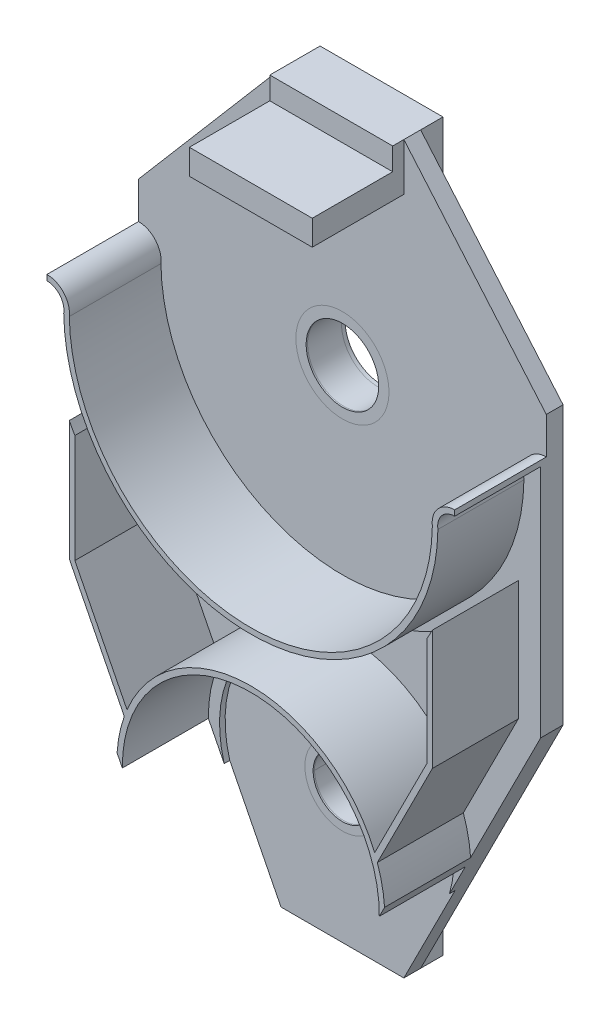
SolidWorks part; units mm, degrees
ref_plane "Piano frontale" through (0, 0, 0) normal (0, 0, 1) x (1, 0, 0)
ref_plane "Piano superiore" through (0, 0, 0) normal (0, 1, 0) x (1, 0, 0)
ref_plane "Piano destro" through (0, 0, 0) normal (1, 0, 0) x (0, 0, -1)
sketch "Piastrone" plane through (0, 0, 0) normal (0, 0, 1) x (1, 0, 0)
  line L0 (-86.2054, 491.905) -> (23.7946, 491.905)
  line L1 (23.7946, 491.905) -> (278.7946, 193.1534)
  line L2 (278.7946, 193.1534) -> (278.7946, -303.2973)
  line L3 (278.7946, -303.2973) -> (23.7946, -808.095)
  line L4 (23.7946, -808.095) -> (-86.2054, -808.095)
  line L5 (-86.2054, 491.905) -> (-86.2054, -808.095) construction
  line L6 (23.7946, -808.095) -> (165.1407, -808.095) construction
  line L7 (-137.1386, 86.905) -> (-47.6935, 86.905) construction
  line L8 (-154.5853, -568.095) -> (-41.1537, -568.095) construction
  line L9 (-86.2054, -808.095) -> (-86.2054, -620.595)
  line L10 (-86.2054, -515.595) -> (-86.2054, 21.905)
  line L11 (-86.2054, 151.905) -> (-86.2054, 491.905)
  arc A1 (-86.2054, 151.905) -> (-86.2054, 21.905) centre (-86.2054, 86.905) cw
  arc A2 (-86.2054, -515.595) -> (-86.2054, -620.595) centre (-86.2054, -568.095) cw
  circle A3 centre (-86.2054, 86.905) radius 170 construction
  circle A4 centre (-86.2054, -568.095) radius 100 construction
  circle A5 centre (-86.2054, 86.905) radius 312.5 construction
  dimension "D7" = 65
  dimension "D9" = 52.5
  dimension "D1" = 340
  dimension "D2" = 200
  dimension "D5" = 1300
  dimension "D3" = 405
  dimension "D4" = 240
  dimension "D6" = 365
  dimension "D8" = 110
extrude "PiastroneExtr" add sketch "Piastrone" along normal blind 30
sketch "Sketch14" plane through (0, 0, 0) normal (0, 0, -1) x (-1, 0, 0)
  line L0 (-23.7946, 491.905) -> (86.2054, 491.905)
  line L1 (86.2054, 491.905) -> (86.2054, 151.905)
  line L2 (86.2054, -808.095) -> (-23.7946, -808.095)
  line L3 (-23.7946, -808.095) -> (-23.7946, 491.905)
  line L4 (86.2054, -620.595) -> (86.2054, -808.095)
  line L5 (86.2054, 21.905) -> (86.2054, -515.595)
  arc A0 (86.2054, 151.905) -> (86.2054, 21.905) centre (86.2054, 86.905) ccw
  arc A1 (86.2054, -515.595) -> (86.2054, -620.595) centre (86.2054, -568.095) ccw
extrude "Lamone" add sketch "Sketch14" along normal blind 40 separate body
ref_axis "Axis1" through (-86.2054, 86.905, 30) along (0, 0, -1)
ref_axis "Axis2" through (-86.2054, -568.095, 30) along (0, 0, -1)
sketch "Carter" plane through (0, 0, 0) normal (0, 0, 1) x (1, 0, 0)
  line L0 (-86.2054, 21.905) -> (-86.2054, -515.595) construction
  line L1 (-86.2054, 21.905) -> (-86.2054, -515.595) construction
  line L8 (278.7946, -303.2973) -> (278.7946, 193.1534) construction
  line L15 (278.7946, 86.905) -> (278.7946, 117.3467)
  line L16 (278.7946, 117.3467) -> (278.7946, 127.2478)
  line L17 (-86.2054, -238.095) -> (-86.2054, -248.095)
  line L18 (-86.2054, -248.095) -> (-86.2054, -278.095)
  circle A0 centre (-86.2054, 86.905) radius 350 construction
  arc A1 (-86.2054, -278.095) -> (278.7946, 86.905) centre (-86.2054, 86.905) ccw
  arc A2 (-86.2054, -248.095) -> (248.758, 81.9556) centre (-86.2054, 86.905) ccw
  arc A6 (-86.2054, -238.095) -> (238.7568, 81.9533) centre (-86.2054, 86.905) ccw
  arc A8 (238.7568, 81.9533) -> (278.7946, 127.2478) centre (278.7946, 86.905) cw
  arc A9 (248.758, 81.9556) -> (278.7946, 117.3467) centre (278.7946, 86.905) cw
  dimension "D1" = 15
  dimension "D2" = 15
  dimension "D3" = 10
extrude "CarterExt1" add sketch "Carter" along normal blind 10 from surface separate body contours A9 A2 L18 A1 L15 | A2 A9 L16 A8 A6 L17 region at (168.0833, -167.3837, 0) region at (251.5934, 109.9908, 0) starting at face at (20.5446, -170.4903, 30)
extrude "CarterExt2" add sketch "Carter<4>" along normal blind 154 from surface contours A2 A9 L16 A8 A6 L17 region at (251.5934, 109.9908, 0) starting at face at (150.9785, -70.6465, 40)
sketch "Carter<4>" plane through (0, 0, 0) normal (0, 0, 1) x (1, 0, 0) same geometry as "Carter"
sketch "ForiCirc1" plane through (0, 0, 0) normal (0, 0, 1) x (1, 0, 0)
  line L0 (-86.2054, 21.905) -> (-86.2054, -515.595) construction
  line L1 (-86.2054, 86.905) -> (-196.5458, 86.905) construction
  line L2 (-86.2054, 86.905) -> (-86.2054, 123.8864) construction
  line L3 (-86.2054, -248.095) -> (-86.2054, -278.095) construction
  circle A0 centre (-86.2054, -262.971) radius 5
  circle A1 centre (-86.2054, 86.905) radius 349.8761 construction
sketch "IrrigidCirc" plane through (0, 0, 0) normal (0, 0, 1) x (1, 0, 0)
  line L0 (23.7946, -808.095) -> (278.7946, -303.2973) construction
  line L1 (-86.2054, 21.905) -> (-86.2054, -515.595) construction
  line L2 (-86.2054, 21.905) -> (-86.2054, -515.595) construction
  line L6 (-86.2054, 21.905) -> (-86.2054, -515.595) construction
  line L10 (-86.2054, -358.095) -> (-86.2054, -338.095)
  line L11 (-86.2054, -338.095) -> (-86.2054, -328.095)
  line L12 (115.4845, -626.5856) -> (143.7813, -570.5695)
  line L13 (143.7813, -570.5695) -> (153.2434, -551.8383)
  arc A0 (115.4845, -626.5856) -> (-86.2054, -358.095) centre (-86.2054, -568.095) ccw
  arc A1 (-86.2054, -338.095) -> (143.7813, -570.5695) centre (-86.2054, -568.095) cw
  circle A2 centre (-86.2054, -568.095) radius 220 construction
  arc A3 (-86.2054, -328.095) -> (153.2434, -551.8383) centre (-86.2054, -568.095) cw
  dimension "D1" = 440
  dimension "D2" = 10
  dimension "D3" = 10
  dimension "D4" = 10
extrude "IrrigidCirc1" add sketch "IrrigidCirc" along normal blind 10 from surface separate body contours A1 L10 A0 L12 | A3 L11 A1 L13 region at (-82.5159, -348.095, 0) region at (-82.7976, -333.095, 0) starting at face at (20.5446, -170.4903, 30)
extrude "IrrigidCirc2" add sketch "IrrigidCirc<7>" along normal up to surface (194 mm away) from surface contours A3 L11 A1 L13 region at (-82.7976, -333.095, 0) up to face at (164.5847, -32.8231, 194) starting at face at (51.8771, -441.7522, 40)
sketch "IrrigidCirc<7>" plane through (0, 0, 0) normal (0, 0, 1) x (1, 0, 0) same geometry as "IrrigidCirc"
sketch "Sketch9" plane through (0, 0, 0) normal (0, 0, 1) x (1, 0, 0)
  line L0 (278.7946, -303.2973) -> (153.2434, -551.8383)
  line L1 (135.4731, -476.1242) -> (228.7946, -291.3853)
  line L2 (228.7946, -291.3853) -> (228.7946, -97.4858)
  line L3 (278.7946, -303.2973) -> (278.7946, 86.905)
  line L4 (23.7946, -808.095) -> (278.7946, -303.2973) construction
  line L5 (228.7946, -291.3853) -> (278.7946, -303.2973) construction
  line L6 (238.7946, -293.7677) -> (238.7946, -79.2274)
  line L7 (238.7946, -293.7677) -> (140.299, -488.7493)
  arc A0 (153.2434, -551.8383) -> (-86.2054, -328.095) centre (-86.2054, -568.095) ccw construction
  arc A4 (-86.2054, -278.095) -> (278.7946, 86.905) centre (-86.2054, 86.905) ccw construction
  arc A5 (228.7946, -97.4858) -> (278.7946, 86.905) centre (-86.2054, 86.905) ccw
  arc A6 (153.2434, -551.8383) -> (135.4731, -476.1242) centre (-86.2054, -568.095) ccw
  dimension "D2" = 50
  dimension "D1" = 50
  dimension "D3" = 10
extrude "IrrigidEsterno1" add sketch "Sketch9" along normal blind 10 from surface separate body contours L6 L5 L3 A5 | L5 L7 A6 L0 | L5 L1 A6 L7 | L2 L5 L6 A5 region at (260.5179, -159.069, 0) region at (203.8433, -409.1021, 0) region at (185.893, -387.5021, 0) region at (233.8788, -190.5027, 0) starting at face at (20.5446, -170.4903, 30)
extrude "IrrigidEsterno2" add sketch "Sketch9<3>" along normal up to surface (194 mm away) from surface contours L2 L5 L6 A5 | L5 L1 A6 L7 region at (185.893, -387.5021, 0) region at (233.8788, -190.5027, 0) up to face at (164.5847, -32.8231, 194) starting at face at (219.8767, -272.6384, 40)
sketch "Sketch9<3>" plane through (0, 0, 0) normal (0, 0, 1) x (1, 0, 0) same geometry as "Sketch9"
sketch "Sketch12" plane through (0, 0, 0) normal (0, 0, 1) x (1, 0, 0)
  line L0 (-86.2054, 491.905) -> (-86.2054, 451.905)
  line L1 (-86.2054, 491.905) -> (-86.2054, 151.905) construction
  line L2 (-86.2054, 451.905) -> (23.7946, 451.905)
  line L3 (23.7946, 491.905) -> (23.7946, 451.905)
  line L4 (23.7946, 471.905) -> (-86.2054, 471.905) construction
  line L5 (-86.2054, 491.905) -> (23.7946, 491.905)
  line L6 (23.7946, 451.905) -> (23.7946, 406.905)
  line L7 (23.7946, 406.905) -> (-86.2054, 406.905)
  line L8 (-86.2054, 406.905) -> (-86.2054, 451.905)
  dimension "D1" = 40
  dimension "D2" = 45
extrude "RinforzoSup1" add sketch "Sketch12" along normal blind 20 from surface separate body contours L8 L7 L6 L2 | L3 L2 L0 L5 region at (-31.2054, 429.405, 0) starting at face at (20.5446, -170.4903, 30)
extrude "Boss-Extrude1" add sketch "Sketch12<4>" along normal up to surface (194 mm away) from surface contours L8 L7 L6 L2 region at (-31.2054, 429.405, 0) up to face at (164.5847, -32.8231, 194) starting at face at (-31.2054, 449.405, 50)
sketch "Sketch12<4>" plane through (0, 0, 0) normal (0, 0, 1) x (1, 0, 0) same geometry as "Sketch12"
combine bodies "Combine11" operation type add bodies to combine 140 101 228 112 123 119
mirror "Mirror3" about plane through (-86.2054, 491.905, -40) normal (1, 0, 0) of bodies 231
sketch "Sketch15" plane through (0, 0, -40) normal (0, 0, -1) x (-1, 0, 0)
  circle A0 centre (86.2054, -568.095) radius 67.215
  circle A1 centre (86.2054, 86.905) radius 83.2994
  circle A3 centre (86.2054, 86.905) radius 65 construction
split line "Split Line1"
sketch "Sketch16" plane through (0, 0, 0) normal (1, 0, 0) x (0, 0, -1)
  line L0 (33.3413, 608.5378) -> (33.3413, -904.3335)
  line L1 (-27.4088, 608.5378) -> (-27.4088, -904.3335)
  point P2 (-65.3482, -904.3335)
  point P5 (33.3413, -904.3335)
split line "Split Line2"
sketch "Sketch17" plane through (0, 0, 0) normal (0, 0, 1) x (1, 0, 0)
  line L0 (33.0219, -566.8586) -> (-223.0649, -569.5141)
split line "Split Line3"
ref_point "Point1"
